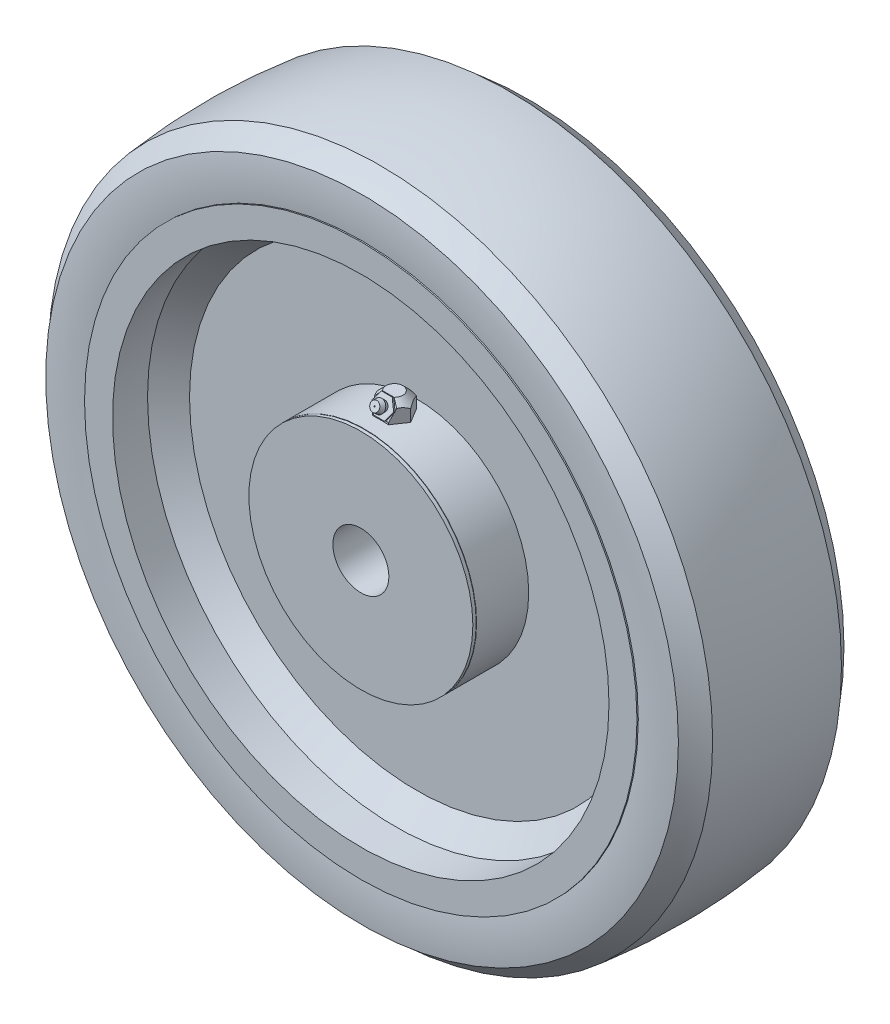
SolidWorks part; units mm, degrees
ref_plane "Front" through (0, 0, 0) normal (0, 0, 1) x (1, 0, 0)
ref_plane "Top" through (0, 0, 0) normal (0, 1, 0) x (1, 0, 0)
ref_plane "Right" through (0, 0, 0) normal (1, 0, 0) x (0, 0, -1)
sketch "Layout" plane through (0, 0, 0) normal (1, 0, 0) x (0, 0, -1)
  line L0 (0, 152.4) -> (0, -152.4) construction
  line L1 (-38.1, 152.4) -> (38.1, 152.4) construction
  line L2 (-38.1, 0) -> (38.1, 0) construction
  line L3 (-38.1, 12.7) -> (0, 12.7) construction
  dimension "Diameter" = 304.8
  dimension "Hub Length" = 76.2
  dimension "Width" = 76.2
  dimension "For Axle" = 25.4
sketch "Sketch2" plane through (0, 0, 0) normal (1, 0, 0) x (0, 0, -1)
  line L0 (0, 12.7) -> (-38.1, 12.7)
  line L1 (-38.1, 12.7) -> (-38.1, 50.8)
  line L2 (-38.1, 50.8) -> (-12.7496, 50.8) construction
  line L3 (-12.7496, 50.8) -> (-12.7496, 112.6148) construction
  line L4 (-12.7496, 112.6148) -> (-38.1496, 112.6148)
  line L5 (-38.1496, 112.6148) -> (-38.1496, 125.3148)
  line L6 (-38.1496, 125.3148) -> (0, 125.3148)
  line L7 (0, 152.4) -> (0, -152.4) construction
  line L8 (0, 125.3148) -> (0, 12.7)
  line L9 (-29.21, 152.4) -> (-38.1, 152.4) construction
  line L10 (-38.1, 152.4) -> (-38.1, 143.51) construction
  line L11 (-38.1, 152.4) -> (38.1, 152.4) construction
  line L12 (-38.1, 143.51) -> (-38.1, 112.6148) construction
  line L13 (0, 152.4) -> (0, -152.4) construction
  line L14 (-29.21, 150.7148) -> (-29.21, 152.4) construction
  line L15 (-37.555, 143.51) -> (-38.1, 143.51) construction
  line L16 (-38.1, 0) -> (38.1, 0) construction
  line L17 (-38.1, 0) -> (38.1, 0) construction
  line L18 (-38.1, 112.6148) -> (-38.1496, 112.6148) construction
  line L19 (-12.7496, 109.4398) -> (-12.7496, 50.8)
  line L20 (-12.7496, 112.6148) -> (-12.7496, 109.4398)
  line L21 (-38.1, 50.8) -> (-36.576, 50.8)
  line L22 (-36.576, 50.8) -> (-36.576, 50.6222)
  line L23 (-36.576, 50.6222) -> (-36.3982, 50.6222)
  line L24 (-36.3982, 50.6222) -> (-36.3982, 50.8)
  line L25 (-36.3982, 50.8) -> (-12.7496, 50.8)
  arc A0 (-29.21, 150.7148) -> (-37.555, 143.51) centre (-99.6809, 223.9023) cw construction
  arc A1 (-37.555, 143.51) -> (-37.555, 125.3148) centre (38.1, 134.4124) ccw construction
  arc A2 (-29.21, 150.7148) -> (0, 152.4) centre (0, -101.6) cw construction
  dimension "D3" = 254
  dimension "D4" = 76.2
  dimension "D6" = 101.6
  dimension "D2" = 8.89
  dimension "D5" = 38.1
  dimension "D7" = 3.175
  dimension "D8" = 12.7
  dimension "D9" = 0.5947
  dimension "D10" = 25.4
  dimension "Hub Thickness" = 50.8
  dimension "D11" = 0.1778
  dimension "D12" = 1.524
revolve "Revolve1" add sketch "Sketch2" angle 360 about L17
sketch "Sketch3" plane through (0, 0, 0) normal (1, 0, 0) x (0, 0, -1)
  line L0 (-37.555, 125.3148) -> (0, 125.3148)
  line L1 (0, 152.4) -> (0, 125.3148)
  line L2 (-38.1, 0) -> (38.1, 0) construction
  line L3 (-38.1, 0) -> (38.1, 0) construction
  arc A0 (0, 152.4) -> (-29.21, 150.7148) centre (0, -101.6) ccw construction
  arc A1 (-37.555, 143.51) -> (-29.21, 150.7148) centre (-99.6809, 223.9023) ccw construction
  arc A2 (-37.555, 143.51) -> (-37.555, 125.3148) centre (38.1, 134.4124) ccw construction
  arc A3 (0, 152.4) -> (-29.21, 150.7148) centre (0, -101.6) ccw
  arc A4 (-37.555, 143.51) -> (-29.21, 150.7148) centre (-99.6809, 223.9023) ccw
  arc A5 (-37.555, 143.51) -> (-37.555, 125.3148) centre (38.1, 134.4124) ccw
revolve "Revolve2" add sketch "Sketch3" angle 360 about L3
mirror "Mirror1" about plane through (0, 0, 0) normal (0, 0, 1) of bodies 110 109
chamfer "Chamfer1" distance 9.525 angle 45 2 edges at (112.6148, 0, 12.7496) (112.6148, 0, -12.7496)
combine bodies "Combine1" operation type add bodies to combine 111 112
sketch "Sketch5" plane through (0, 0, 0) normal (0, 1, 0) x (1, 0, 0)
  line L0 (0, -22.86) -> (0, 0) construction
  line L1 (7.3323, -22.86) -> (3.6662, -16.51)
  line L2 (3.6662, -16.51) -> (-3.6662, -16.51)
  line L3 (-3.6662, -16.51) -> (-7.3323, -22.86)
  line L4 (-7.3323, -22.86) -> (-3.6662, -29.21)
  line L5 (-3.6662, -29.21) -> (3.6662, -29.21)
  line L6 (3.6662, -29.21) -> (7.3323, -22.86)
  circle A0 centre (0, -22.86) radius 6.35 construction
  dimension "D1" = 12.7
  dimension "D2" = 22.86
extrude "Boss-Extrude1" add sketch "Sketch5" along normal blind 50.292 from offset 8.89 separate body
sketch "Sketch10" plane through (0, 0, 38.1) normal (0, 0, 1) x (1, 0, 0)
  circle A0 centre (0, 0) radius 12.7 construction
  circle A1 centre (0, 0) radius 12.7
extrude "Cut-Extrude4" cut sketch "Sketch10" against normal blind 330.2
sketch "Sketch6" plane through (0, 59.182, 0) normal (0, 1, 0) x (1, 0, 0)
  line L0 (-3.6662, -29.21) -> (3.6662, -29.21) construction
  line L2 (7.3323, -22.86) -> (3.6662, -16.51) construction
  line L3 (-3.6662, -16.51) -> (-7.3323, -22.86) construction
  circle A0 centre (0, -22.86) radius 6.35 construction
  circle A1 centre (0, -22.86) radius 3.81
  dimension "D1" = 7.62
extrude "Cut-Extrude2" cut sketch "Sketch6" against normal through all draft 45 flip side to cut
sketch "Sketch7" plane through (0, 0, 0) normal (1, 0, 0) x (0, 0, -1)
  line L0 (-25.4, 59.69) -> (-29.5455, 50.8)
  line L1 (-25.4, 59.69) -> (-33.02, 59.69)
  line L2 (-33.02, 59.69) -> (-33.02, 50.8)
  line L3 (-33.02, 50.8) -> (-29.5455, 50.8)
  line L5 (0, 0) -> (-33.02, 0) construction
  line L6 (-33.02, 0) -> (-33.02, 50.8) construction
  dimension "D1" = 33.02
  dimension "D2" = 8.89
  dimension "D3" = 59.69
  dimension "D4" = 115
  dimension "D5" = 7.62
extrude "Cut-Extrude3" cut sketch "Sketch7" against normal through all both and the other way through all contours L0 L3 L2 L1
sketch "Sketch8" plane through (0, 20.3898, 43.726) normal (0, 0.4226, 0.9063) x (1, 0, 0)
  line L1 (2.4407, 34.3478) -> (4.8813, 38.5751)
  line L2 (4.8813, 38.5751) -> (2.4407, 42.8025)
  line L3 (2.4407, 42.8025) -> (-2.4407, 42.8025)
  line L4 (-2.4407, 42.8025) -> (-4.8813, 38.5751)
  line L5 (-4.8813, 38.5751) -> (-2.4407, 34.3478)
  line L6 (-2.4407, 34.3478) -> (2.4407, 34.3478)
  line L7 (-3.6662, 34.3478) -> (3.6662, 34.3478) construction
  line L8 (0, 42.8025) -> (0, 34.3478) construction
  line L9 (-2.6086, 42.8025) -> (2.6086, 42.8025) construction
  circle A0 centre (0, 38.5751) radius 4.2274 construction
extrude "Boss-Extrude2" add sketch "Sketch8" along normal blind 0.762
sketch "Sketch9" plane through (0, 0, 0) normal (1, 0, 0) x (0, 0, -1)
  line L0 (-26.3275, 59.504) -> (-28.114, 55.6727) construction
  line L1 (-26.3275, 59.504) -> (-28.114, 55.6727) construction
  line L2 (-28.114, 55.6727) -> (-12.6716, 48.4718) construction
  line L3 (-27.2208, 57.5884) -> (-28.6598, 59.0101)
  line L4 (-28.6598, 59.0101) -> (-30.904, 59.3059)
  line L5 (-30.904, 59.3059) -> (-31.6899, 57.6205)
  line L6 (-31.6899, 57.6205) -> (-31.4597, 57.5131)
  line L7 (-31.4597, 57.5131) -> (-31.5671, 57.2829)
  line L8 (-31.5671, 57.2829) -> (-28.114, 55.6727)
  line L9 (-28.6598, 59.0101) -> (-29.8406, 56.4778) construction
  line L10 (-30.904, 59.3059) -> (-27.2208, 57.5884) construction
  line L11 (-27.2208, 57.5884) -> (-28.114, 55.6727)
  dimension "D1" = 2.794
  dimension "D2" = 3.81
  dimension "D3" = 0.254
revolve "Revolve3" add sketch "Sketch9" angle 360 about L2
